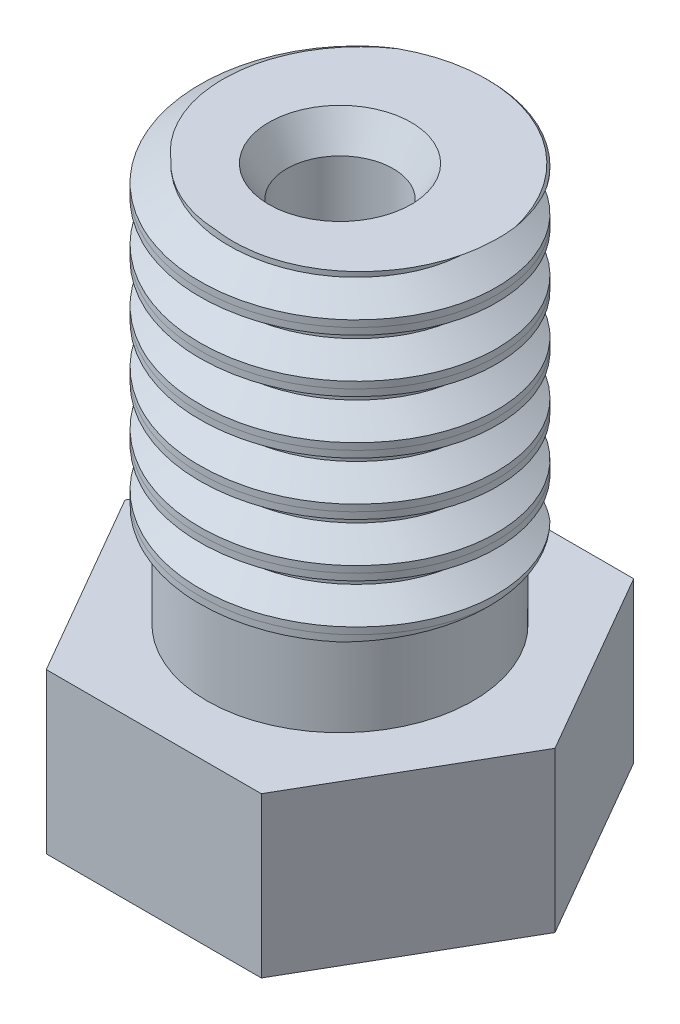
SolidWorks part; units mm, degrees
ref_plane "Plano frontal" through (0, 0, 0) normal (0, 0, 1) x (1, 0, 0)
ref_plane "Plano superior" through (0, 0, 0) normal (0, 1, 0) x (1, 0, 0)
ref_plane "Plano direito" through (0, 0, 0) normal (1, 0, 0) x (0, 0, -1)
sketch "Esboço1" plane through (0, 0, 0) normal (0, 0, 1) x (1, 0, 0)
  line L0 (-89.0288, -25.746) -> (-89.0288, -36.246) construction
  dimension "D1" = 10.5
sketch "Esboço2" plane through (0, 0, 0) normal (0, 0, -1) x (-1, 0, 0)
  line L0 (-93.6392, -16.6385) -> (-93.6392, -30.0868) construction
  line L1 (-94.9769, -17.5757) -> (-96.6392, -17.5757)
  line L2 (-96.6392, -17.5757) -> (-96.6392, -23.3937)
  line L4 (-96.1392, -23.3937) -> (-96.1392, -25.0757)
  line L5 (-96.1392, -25.0757) -> (-97.1392, -25.0757)
  line L6 (-97.1392, -25.0757) -> (-97.1392, -28.0757)
  line L7 (-97.1392, -28.0757) -> (-95.5396, -28.0757)
  line L8 (-95.5396, -28.0757) -> (-94.1392, -30.0757)
  line L9 (-94.1392, -30.0757) -> (-93.8392, -30.0757)
  line L10 (-93.8392, -30.0757) -> (-93.8392, -29.2757)
  line L11 (-93.8392, -29.2757) -> (-94.3892, -28.8612)
  line L12 (-94.3892, -28.8612) -> (-94.3892, -28.2641)
  line L13 (-94.3892, -28.2641) -> (-94.6392, -28.0757)
  line L14 (-94.6392, -28.0757) -> (-94.6392, -18.1607)
  line L15 (-94.6392, -18.1607) -> (-94.9769, -17.5757)
  line L16 (-96.6392, -23.3937) -> (-96.1392, -23.3937)
  dimension "D1" = 1
  dimension "D2" = 12.5
  dimension "D3" = 10.5
  dimension "D4" = 125
  dimension "D5" = 2.5
  dimension "D7" = 7.5
  dimension "D8" = 3.5
  dimension "D9" = 0.8
  dimension "D10" = 0.4
  dimension "D11" = 1
  dimension "D12" = 1.5
  dimension "D14" = 127
  dimension "D15" = 3
  dimension "D16" = 150
revolve "Revolução1" add sketch "Esboço2" angle 360 about L0
sketch "Esboço4" plane through (0, -28.0757, 0) normal (0, -1, 0) x (-1, 0, 0)
  line L1 (91.6185, 3.5) -> (89.5977, 0)
  line L2 (89.5977, 0) -> (91.6185, -3.5)
  line L3 (91.6185, -3.5) -> (95.6599, -3.5)
  line L4 (95.6599, -3.5) -> (97.6806, 0)
  line L5 (97.6806, 0) -> (95.6599, 3.5)
  line L6 (95.6599, 3.5) -> (91.6185, 3.5)
  circle A0 centre (93.6392, 0) radius 3.5 construction
extrude "Corte-extrusão1" [suppressed] cut sketch "Esboço4" against normal blind 3.5 flip side to cut
ref_plane "Plano1" through (0, -24.2757, 0) normal (0, 1, 0) x (1, 0, 0)
chamfer "Chanfro1" distance 0.25 angle 45 1 edges at (93.6392, -17.5757, 3)
sketch "Esboço5" plane through (0, 0, 0) normal (0, 0, 1) x (1, 0, 0)
  line L0 (91.3897, -23.4562) -> (90.8485, -23.7687)
  line L1 (90.632, -23.8937) -> (90.632, -22.8937)
  line L2 (91.3897, -23.3937) -> (90.632, -23.3937) construction
  line L3 (91.3897, -23.3312) -> (90.8485, -23.0187)
  line L4 (91.3897, -23.3312) -> (91.3897, -23.4562)
  line L5 (90.632, -23.8937) -> (90.8485, -23.8937)
  line L6 (90.8485, -23.8937) -> (90.8485, -23.7687)
  line L7 (90.8485, -22.8937) -> (90.8485, -23.0187)
  line L8 (90.632, -22.8937) -> (90.8485, -22.8937)
  line L10 (90.8485, -23.0187) -> (90.8485, -23.7687) construction
  line L11 (94.2734, -23.3937) -> (88.2734, -23.3937) construction
  dimension "D1" = 0.5
  dimension "D2" = 0.125
  dimension "D3" = 0.125
sketch "Esboço6" plane through (0, -24.2757, 0) normal (0, 1, 0) x (1, 0, 0)
  circle A1 centre (93.6392, 0) radius 3
curve "Hélice/Espiral1" pitch 1 height 9 radius 3 left hand yes centre (93.6392, -24.2757, 0) axis (0, 1, 0) start towards (0, 0, 1)
sweep "Varredura de corte2" cut profiles "Esboço5" path "Hélice/Espiral1" align with end faces yes
sketch "Esboço7" plane through (0, -25.0757, 0) normal (0, 1, 0) x (1, 0, 0)
  circle A0 centre (93.6392, 0) radius 2.5
  circle A1 centre (93.6392, 0) radius 1.585
extrude "Ressalto-extrusão3" add sketch "Esboço7" along normal up to vertex (1.682 mm away) up to point (95.6125, -23.3937, 1.9733)
sketch "Esboço3" plane through (0, -25.0757, 0) normal (0, 1, 0) x (1, 0, 0)
  line L1 (89.5977, 0) -> (91.6185, -3.5)
  line L2 (91.6185, -3.5) -> (95.6599, -3.5)
  line L3 (95.6599, -3.5) -> (97.6806, 0)
  line L4 (97.6806, 0) -> (95.6599, 3.5)
  line L5 (95.6599, 3.5) -> (91.6185, 3.5)
  line L6 (91.6185, 3.5) -> (89.5977, 0)
  circle A0 centre (93.6392, 0) radius 3.5 construction
  circle A1 centre (93.6392, 0) radius 2.5559
  dimension "D1" = 7
extrude "Ressalto-extrusão1" add sketch "Esboço3" against normal up to surface (3 mm away) up to face at (93.6392, -28.0757, 1.9004)
sketch "Esboço8" plane through (0, 0, 3.5) normal (0, 0, 1) x (1, 0, 0)
  line L0 (91.6185, -25.0757) -> (95.6599, -25.0757) construction
  line L1 (93.1392, -25.5757) -> (94.1392, -25.5757)
  line L2 (93.1392, -25.5757) -> (93.1392, -24.5757)
  line L3 (93.1392, -24.5757) -> (94.1392, -24.5757)
  line L4 (94.1392, -25.5757) -> (94.1392, -24.5757)
  line L5 (93.1392, -25.5757) -> (94.1392, -24.5757) construction
  line L6 (93.1392, -24.5757) -> (94.1392, -25.5757) construction
  point P0 (93.6392, -25.0757)
  dimension "D1" = 1
  dimension "D2" = 1
extrude "Corte-extrusão2" [suppressed] cut sketch "Esboço8" against normal blind 1
